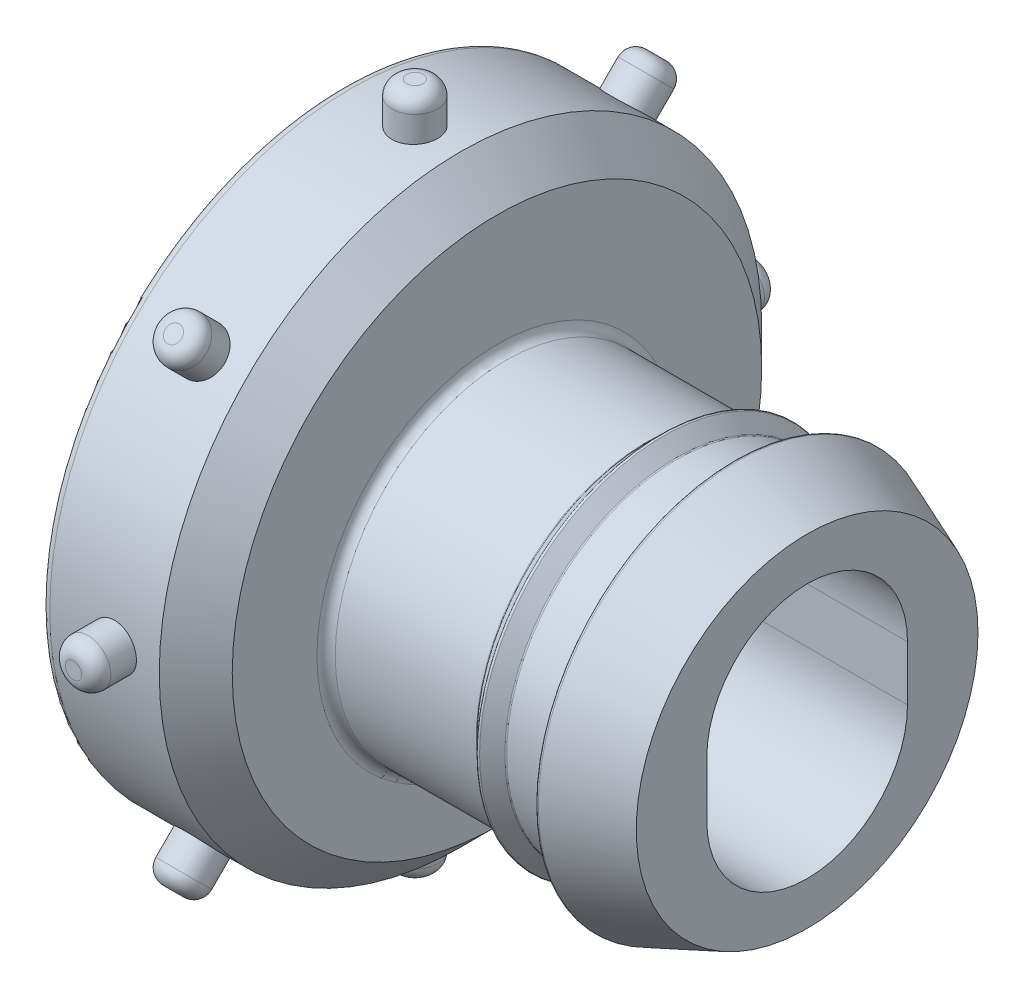
SolidWorks part; units mm, degrees
note: '?' marks a value the reader was unsure of. The reader was unsure of these and kept them because the rebuilt part matched: shared geometry of "Sketch2<3>".
ref_plane "Front Plane" through (0, 0, 0) normal (0, 0, 1) x (1, 0, 0)
ref_plane "Top Plane" through (0, 0, 0) normal (0, 1, 0) x (1, 0, 0)
ref_plane "Right Plane" through (0, 0, 0) normal (1, 0, 0) x (0, 0, -1)
sketch "Sketch1" plane through (0, 0, 0) normal (0, 1, 0) x (1, 0, 0)
  line L0 (0, 0) -> (-17, 0)
  line L1 (0, 0) -> (0, 9.365)
  line L2 (0, 9.365) -> (-3.97, 10.955)
  line L3 (-3.97, 10.955) -> (-3.97, 9.365)
  line L4 (0, 9.365) -> (-19.3321, 9.365) construction
  line L5 (-3.97, 9.365) -> (-7.15, 9.365)
  line L6 (-7.15, 9.365) -> (-7.94, 10.155)
  line L7 (-7.94, 10.155) -> (-8.73, 9.365)
  line L8 (-8.73, 9.365) -> (-17, 9.365)
  line L9 (-17, 9.365) -> (-17, 0)
  dimension "D1" = 17
  dimension "D2" = 9.365
  dimension "D3" = 1.59
  dimension "D4" = 3.97
  dimension "D5" = 7.94
  dimension "D6" = 0.79
revolve "Revolve1" add sketch "Sketch1" angle 360 about L0
sketch "Sketch2" plane through (-17, 0, 0) normal (-1, 0, 0) x (0, 0, 1)
  line L0 (0, 0) -> (0, 4.1864) construction
  line L1 (5.5, 1.5) -> (5.5, 0)
  line L3 (-5.5, 1.5) -> (-5.5, 0)
  line L4 (5.5, 0) -> (5.5, -1.5)
  line L5 (-5.5, -1.5) -> (-5.5, 0)
  circle A0 centre (0, 1.5) radius 9.365
  arc A1 (-5.5, 0) -> (-5.4486, -0.75) centre (0, 0) ccw
  circle A3 centre (0, 1.5) radius 16.51
  circle A4 centre (0, 0) radius 9.365 construction
  arc A6 (5.5, 1.5) -> (-5.5, 1.5) centre (0, 1.5) ccw
  arc A7 (-5.5, -1.5) -> (5.5, -1.5) centre (0, -1.5) ccw
  dimension "D1" = 11
  dimension "D2" = 33.02
  dimension "D3" = 1.5
  dimension "D4" = 1.5
extrude "Boss-Extrude1" add sketch "Sketch2" along normal blind 8.5
ref_axis "Axis1" through (-25.5, -17.1251, 0) along (0, 1, 0)?
sketch "Sketch4" plane through (-25.5, 0, 0) normal (-1, 0, 0) x (0, 0, 1)
  line L0 (0, -17.1251) -> (0, 19.1969) construction
  line L1 (9.09, 7.6298) -> (-9.09, 7.6298)
  line L2 (9.09, 7.6298) -> (9.09, -5.5702)
  line L3 (9.09, -5.5702) -> (-9.09, -5.5702)
  line L4 (-9.09, 7.6298) -> (-9.09, -5.5702)
  point P6 (0, 7.6298)
  dimension "D1" = 18.18
  dimension "D2" = 13.2
extrude "Cut-Extrude1" cut sketch "Sketch4" against normal blind 7
sketch "Sketch5" plane through (-25.5, 0, 0) normal (-1, 0, 0) x (0, 0, 1)
  line L0 (0, -17.1251) -> (0, 19.1969) construction
  circle A0 centre (0, 1.5) radius 14.14
  dimension "D1" = 28.28
  dimension "D2" = 1.5
sketch "Sketch6" plane through (0, 0, 0) normal (0, 0, 1) x (1, 0, 0)
  line L0 (-25.5, 15.64) -> (-25.5, -12.64) construction
  circle A0 centre (-25.5, 15.64) radius 0.9
  point P0 (-25.5, 15.64)
  dimension "D1" = 1.8
ref_axis "Axis2" through (-25.5, 1.5, 0) along (1, 0, 0)
revolve "Cut-Revolve1" cut sketch "Sketch6" angle 360 about axis through (-25.5, 1.5, 0) along (1, 0, 0)
ref_plane "Plane1" through (-21.5, 0, 0) normal (-1, 0, 0) x (0, 0, 1)
ref_axis "Axis3" through (-21.5, -18.3, 0) along (0, 1, 0)?
ref_plane "Plane2" through (0, 18.01, 0) normal (0, 1, 0) x (1, 0, 0)
sketch "Sketch7" plane through (0, 18.01, 0) normal (0, 1, 0) x (1, 0, 0)
  circle A0 centre (-21.5, 0) radius 1.25
  dimension "D1" = 2.5
extrude "Boss-Extrude2" add sketch "Sketch7" along normal blind 2.2 and the other way blind 2 contours A0
fillet "Fillet2" radius 0.8 1 edges at (-21.5, 20.21, 1.25)
pattern_circular "CirPattern1" count 8 over 360 about axis through (0, 1.5, 0) along (1, 0, 0) of "Boss-Extrude2", "Fillet2"
fillet "Fillet4" radius 0.1 5 edges at (-8.73, 0, -9.365) (-7.94, 0, -10.155) (-7.15, 0, -9.365) (-3.97, 0, -9.365) (-3.97, 0, -10.955)
extrude "Cut-Extrude2" cut sketch "Sketch2<3>" against normal through all both and the other way through all
sketch "Sketch2<3>" plane through (-17, 0, 0) normal (-1, 0, 0) x (0, 0, 1) same geometry as "Sketch2"
sketch "Sketch8" plane through (-18.5, 0, 0) normal (-1, 0, 0) x (0, 0, 1)
  line L0 (-5.5, 1.5) -> (-5.5, -1.5) construction
  line L1 (-9.09, -5.5702) -> (-5.5, -5.5702)
  line L2 (-9.09, -5.5702) -> (-9.09, 2.0798)
  line L3 (-9.09, 2.0798) -> (-5.5, 2.0798)
  line L4 (-5.5, -5.5702) -> (-5.5, 2.0798)
  line L9 (5.5, -1.5) -> (5.5, 1.5) construction
  line L13 (9.09, -5.5702) -> (5.5, -5.5702)
  line L14 (9.09, -5.5702) -> (9.09, 2.0798)
  line L15 (9.09, 2.0798) -> (5.5, 2.0798)
  line L16 (5.5, -5.5702) -> (5.5, 2.0798)
  dimension "D1" = 7.65
extrude "Boss-Extrude3" add sketch "Sketch8" along normal blind 0.64
fillet "Fillet5" radius 0.5 2 edges at (-19.14, 2.0798, 7.295) (-19.14, -1.7452, 5.5)
fillet "Fillet6" radius 0.5 1 edges at (-17, 0, 9.365)
chamfer "Chamfer1" distance 2 angle 45 1 edges at (-17, 1.5, 16.51)
fillet "Fillet7" radius 1 1 edges at (-25.5, 1.5, -13.24)
chamfer "Chamfer2" distance 1 distance2 6 1 edges at (-25.5, 7.6298, 0)
fillet "Fillet8" radius 0.5 1 edges at (-25.5, 1.5, 16.51)
equation "\"WallThick\"= 1.2'thickness of wall for printer"
equation "\"dHole\"= 3.3'diameter of screw hole"
equation "\"D1@Boss-Extrude2\"=(37.42-33.02)/2"
